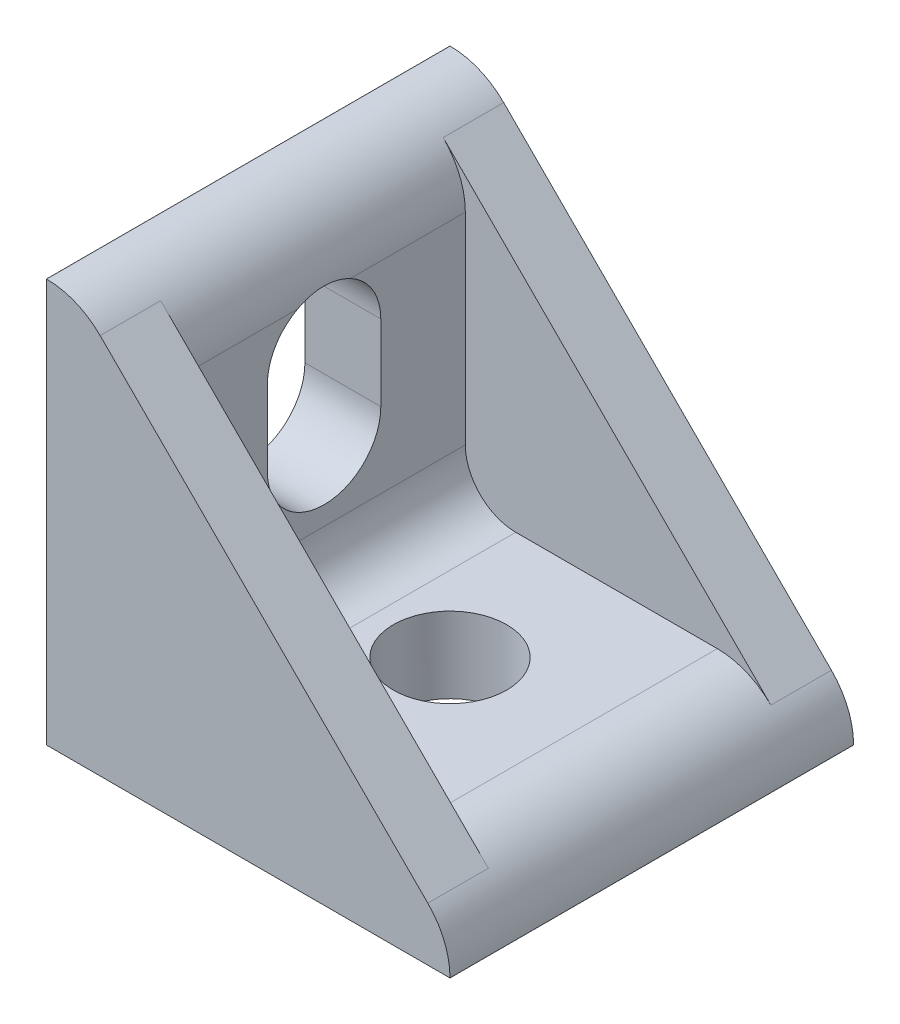
SolidWorks part; units mm, degrees
material "6105-T5 Aluminum"
ref_plane "Front Plane" through (0, 0, 0) normal (0, 0, 1) x (1, 0, 0)
ref_plane "Top Plane" through (0, 0, 0) normal (0, 1, 0) x (1, 0, 0)
ref_plane "Right Plane" through (0, 0, 0) normal (1, 0, 0) x (0, 0, -1)
sketch "Sketch2" plane through (0, 0, 0) normal (0, 0, 1) x (1, 0, 0)
  line L0 (0, 0) -> (0, 25.4)
  line L1 (25.4, 0.0127) -> (25.4, 0)
  line L2 (4.7752, 20.6375) -> (4.7752, 7.9502)
  line L3 (7.9502, 4.7752) -> (20.6375, 4.7752)
  line L4 (0, 25.4) -> (0.0127, 25.4)
  line L5 (25.4, 0) -> (0, 0)
  arc A0 (20.6375, 4.7752) -> (25.4, 0.0127) centre (20.6375, 0.0127) cw
  arc A1 (4.7752, 20.6375) -> (0.0127, 25.4) centre (0.0127, 20.6375) ccw
  arc A2 (4.7752, 7.9502) -> (7.9502, 4.7752) centre (7.9502, 7.9502) ccw
  dimension "D3" = 25.4
  dimension "D4" = 3.175
  dimension "D6" = 4.7625
  dimension "D1" = 4.7752
  dimension "D2" = 4.7752
  dimension "D5" = 25.4
extrude "Boss-Extrude1" add sketch "Sketch2" along normal mid plane 22.225
sketch "Sketch3" plane through (0, 0, 0) normal (-1, 0, 0) x (0, 0, 1)
  line L0 (11.1125, 0) -> (-11.1125, 0) construction
  line L1 (-3.5687, 17.4752) -> (-3.5687, 12.7)
  line L2 (3.5687, 17.4752) -> (3.5687, 12.7)
  line L3 (0, 12.7) -> (0, 0) construction
  arc A0 (3.5687, 17.4752) -> (-3.5687, 17.4752) centre (0, 17.4752) ccw
  arc A1 (-3.5687, 12.7) -> (3.5687, 12.7) centre (0, 12.7) ccw
  dimension "D3" = 12.7
  dimension "D1" = 7.1374
  dimension "D2" = 4.7752
extrude "Cut-Extrude1" cut sketch "Sketch3" against normal up to next
sketch "Sketch4" plane through (0, 0, 0) normal (0, -1, 0) x (1, 0, 0)
  line L0 (0, 11.1125) -> (0, -11.1125) construction
  line L2 (0, 0) -> (12.7, 0) construction
  circle A0 centre (12.7, 0) radius 3.5687
  dimension "D1" = 7.1374
  dimension "D2" = 12.7
extrude "Cut-Extrude2" cut sketch "Sketch4" against normal through all
sketch "Sketch5" plane through (0, 0, 0) normal (0, -1, 0) x (1, 0, 0)
  line L0 (25.4, 11.1125) -> (25.4, -11.1125) construction
  line L1 (0, 12.7) -> (25.4, 12.7)
  line L2 (0, 12.7) -> (0, -12.7)
  line L3 (0, -12.7) -> (25.4, -12.7)
  line L4 (25.4, 12.7) -> (25.4, -12.7)
  line L5 (0, 11.1125) -> (0, -11.1125) construction
  line L7 (25.4, -12.7) -> (0, -12.7)
  line L8 (25.4, -12.7) -> (25.4, -8.89)
  line L9 (25.4, -8.89) -> (0, -8.89)
  line L10 (0, -12.7) -> (0, -8.89)
  line L11 (0, 12.7) -> (25.4, 12.7)
  line L12 (0, 12.7) -> (0, 8.89)
  line L13 (0, 8.89) -> (25.4, 8.89)
  line L14 (25.4, 12.7) -> (25.4, 8.89)
  point P6 (0, 0)
  dimension "D1" = 25.4
  dimension "D2" = 3.81
  dimension "D3" = 3.81
sketch "Sketch6" plane through (0, 0, -11.1125) normal (0, 0, -1) x (-1, 0, 0)
  line L0 (-24.0051, 3.3803) -> (-3.3803, 24.0051)
  line L6 (-25.4, 0) -> (0, 0)
  line L7 (0, 0) -> (0, 25.4)
  line L8 (0, 25.4) -> (-0.0127, 25.4)
  line L9 (-4.7752, 20.6375) -> (-4.7752, 7.9502)
  line L10 (-7.9502, 4.7752) -> (-20.6375, 4.7752)
  line L11 (-25.4, 0.0127) -> (-25.4, 0)
  line L12 (-25.4, 0) -> (0, 0)
  line L13 (0, 0) -> (0, 25.4)
  line L14 (0, 25.4) -> (-0.0127, 25.4)
  line L15 (-4.7752, 20.6375) -> (-4.7752, 7.9502)
  line L16 (-7.9502, 4.7752) -> (-20.6375, 4.7752)
  line L17 (-25.4, 0.0127) -> (-25.4, 0)
  arc A0 (-20.6375, 4.7752) -> (-25.4, 0.0127) centre (-20.6375, 0.0127) ccw construction
  arc A3 (-0.0127, 25.4) -> (-4.7752, 20.6375) centre (-0.0127, 20.6375) ccw
  arc A4 (-7.9502, 4.7752) -> (-4.7752, 7.9502) centre (-7.9502, 7.9502) ccw
  arc A5 (-20.6375, 4.7752) -> (-25.4, 0.0127) centre (-20.6375, 0.0127) ccw
  arc A6 (-0.0127, 25.4) -> (-4.7752, 20.6375) centre (-0.0127, 20.6375) ccw
  arc A7 (-7.9502, 4.7752) -> (-4.7752, 7.9502) centre (-7.9502, 7.9502) ccw
  arc A8 (-20.6375, 4.7752) -> (-25.4, 0.0127) centre (-20.6375, 0.0127) ccw
  dimension "D1" = 0
ref_plane "Plane1" through (0, 0, -12.7) normal (0, 0, 1) x (1, 0, 0)
ref_plane "Plane2" through (0, 0, 12.7) normal (0, 0, 1) x (1, 0, 0)
sketch "Sketch7" plane through (0, 0, -12.7) normal (0, 0, 1) x (1, 0, 0)
  line L0 (24.0051, 3.3803) -> (3.3803, 24.0051) construction
  line L1 (24.0051, 3.3803) -> (3.3803, 24.0051)
  line L6 (0, 0) -> (25.4, 0)
  line L7 (0, 25.4) -> (0, 0)
  line L8 (0.0127, 25.4) -> (0, 25.4)
  line L9 (4.7752, 7.9502) -> (4.7752, 20.6375)
  line L10 (20.6375, 4.7752) -> (7.9502, 4.7752)
  line L11 (25.4, 0) -> (25.4, 0.0127)
  line L12 (0, 0) -> (25.4, 0)
  line L13 (0, 25.4) -> (0, 0)
  line L14 (0.0127, 25.4) -> (0, 25.4)
  line L15 (4.7752, 7.9502) -> (4.7752, 20.6375)
  line L16 (20.6375, 4.7752) -> (7.9502, 4.7752)
  line L17 (25.4, 0) -> (25.4, 0.0127)
  arc A0 (25.4, 0.0127) -> (20.6375, 4.7752) centre (20.6375, 0.0127) ccw construction
  arc A1 (25.4, 0.0127) -> (20.6375, 4.7752) centre (20.6375, 0.0127) ccw
  arc A3 (4.7752, 20.6375) -> (0.0127, 25.4) centre (0.0127, 20.6375) ccw
  arc A4 (4.7752, 7.9502) -> (7.9502, 4.7752) centre (7.9502, 7.9502) ccw
  arc A5 (25.4, 0.0127) -> (20.6375, 4.7752) centre (20.6375, 0.0127) ccw
  arc A6 (4.7752, 20.6375) -> (0.0127, 25.4) centre (0.0127, 20.6375) ccw
  arc A7 (4.7752, 7.9502) -> (7.9502, 4.7752) centre (7.9502, 7.9502) ccw
  arc A8 (25.4, 0.0127) -> (20.6375, 4.7752) centre (20.6375, 0.0127) ccw
  dimension "D1" = 0
extrude "Boss-Extrude2" add sketch "Sketch7" along normal blind 3.81 contours A7 L15 A6 L14 L13 L12 L17 A1 L16 | L15 A7 L16 A1 L1 A6 region at (10.8091, 10.8091, -12.7) region at (24.7056, 1.6978, -12.7)
mirror "Mirror1" about plane through (0, 0, 0) normal (0, 0, 1) of "Boss-Extrude2"
